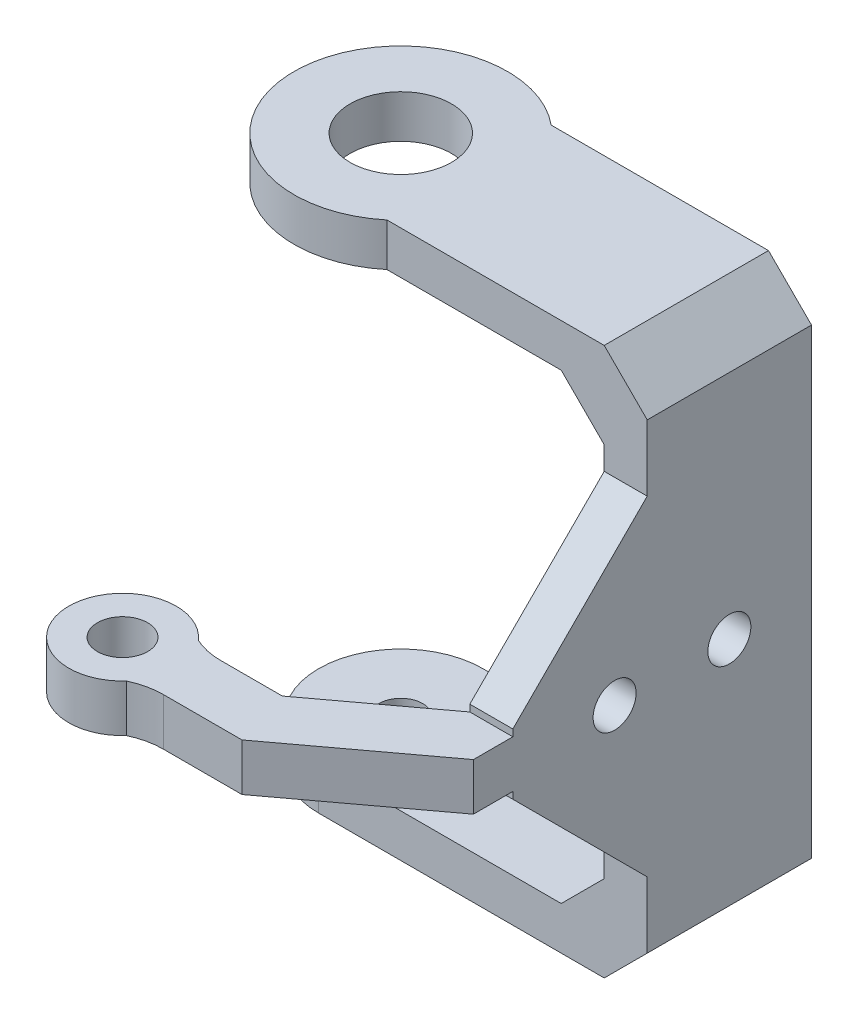
SolidWorks part; units mm, degrees
ref_plane "Front Plane" through (0, 0, 0) normal (0, 0, 1) x (1, 0, 0)
ref_plane "Top Plane" through (0, 0, 0) normal (0, 1, 0) x (1, 0, 0)
ref_plane "Right Plane" through (0, 0, 0) normal (1, 0, 0) x (0, 0, -1)
sketch "Sketch1" plane through (0, 0, 0) normal (0, 0, 1) x (1, 0, 0)
  line L0 (32.1661, 36.798) -> (35.1661, 39.798)
  line L1 (35.1661, 39.798) -> (38.1661, 36.798)
  line L2 (38.1661, 36.798) -> (38.1661, 4.578)
  line L3 (38.1661, 4.578) -> (35.1661, 1.578)
  line L4 (35.1661, 1.578) -> (32.1661, 4.578)
  line L5 (32.1661, 4.578) -> (35.1661, 7.578)
  line L6 (35.1661, 7.578) -> (35.1661, 33.798)
  line L7 (35.1661, 33.798) -> (32.1661, 36.798)
extrude "Boss-Extrude1" add sketch "Sketch1" along normal blind 5.73 and the other way blind 5.73
sketch "Sketch2" plane through (0, 0, 5.73) normal (0, 0, 1) x (1, 0, 0)
  line L0 (32.1661, 36.798) -> (20.0061, 36.798)
  line L2 (32.1661, 39.7973) -> (35.1655, 39.7973)
  line L3 (35.1661, 39.798) -> (32.1661, 36.798) construction
  line L4 (32.1661, 39.7973) -> (20.0061, 39.7973)
  line L5 (20.0061, 39.7973) -> (20.0061, 36.798)
  line L6 (35.1655, 39.7973) -> (32.1661, 36.798)
extrude "Boss-Extrude2" add sketch "Sketch2" against normal up to vertex (11.46 mm away) up to point (32.1661, 36.798, -5.73)
sketch "Sketch3" plane through (0, 0, 5.73) normal (0, 0, 1) x (1, 0, 0)
  line L0 (32.1661, 4.578) -> (35.1661, 1.578)
  line L1 (35.1661, 1.578) -> (32.1661, 1.578)
  line L3 (32.1661, 4.578) -> (20.0061, 4.578)
  line L4 (20.0061, 4.578) -> (20.0061, 1.578)
  line L5 (20.0061, 1.578) -> (32.1661, 1.578)
extrude "Boss-Extrude3" add sketch "Sketch3" against normal up to vertex (11.46 mm away) up to point (32.1661, 4.578, -5.73)
sketch "Sketch4" plane through (0, 39.7973, 0) normal (0, 1, 0) x (1, 0, 0)
  line L0 (20.0061, 5.73) -> (20.0061, -5.73)
  arc A0 (20.0061, 5.73) -> (20.0061, -5.73) centre (15.2449, 0) ccw
extrude "Boss-Extrude4" add sketch "Sketch4" against normal up to vertex (2.9993 mm away) up to point (20.0061, 36.798, 5.73)
sketch "Sketch7" plane through (0, 39.7973, 0) normal (0, 1, 0) x (1, 0, 0)
  circle A1 centre (15.2449, 0) radius 3.54
extrude "Cut-Extrude2" cut sketch "Sketch7" against normal up to vertex (2.9993 mm away) up to point (20.0061, 36.798, -5.73)
sketch "Sketch9" plane through (0, 1.578, 0) normal (0, -1, 0) x (-1, 0, 0)
  line L0 (-20.0061, -5.73) -> (-15.2449, -5.73)
  line L2 (-15.2449, 5.73) -> (-20.0061, 5.73)
  line L3 (-20.0061, 5.73) -> (-20.0061, -5.73)
  arc A0 (-15.2449, -5.73) -> (-15.2449, 5.73) centre (-15.2449, 0) ccw
extrude "Boss-Extrude5" add sketch "Sketch9" against normal blind 3 contours L0 A0 L2 L3
sketch "Sketch11" plane through (0, 1.578, 0) normal (0, -1, 0) x (-1, 0, 0)
  circle A1 centre (-15.2449, 0) radius 1.52
extrude "Cut-Extrude3" cut sketch "Sketch11" against normal blind 3
sketch "Sketch12" plane through (38.1661, 0, 0) normal (1, 0, 0) x (0, 0, -1)
  line L0 (-5.73, 32.188) -> (-5.73, 9.188)
  line L1 (-5.73, 4.578) -> (-5.73, 36.798) construction
  line L2 (-15.1062, 22.8118) -> (-15.1062, 18.5642)
  line L3 (-5.73, 32.188) -> (-15.1062, 22.8118)
  line L4 (-5.73, 9.188) -> (-15.1062, 18.5642)
extrude "Boss-Extrude6" add sketch "Sketch12" against normal up to vertex (3 mm away) up to point (35.1661, 33.798, 5.73)
ref_plane "Plane1" through (0, 20.688, 0) normal (0, -1, 0) x (-1, 0, 0)
sketch "Sketch15" plane through (0, 20.688, 0) normal (0, -1, 0) x (-1, 0, 0)
  line L0 (-35.1661, -15.1062) -> (-38.1661, -15.1062)
  line L1 (-38.1661, -15.1062) -> (-38.1661, -17.8562)
  line L2 (-38.1661, -17.8562) -> (-28.9052, -24.7415)
  line L3 (-35.1661, -15.1062) -> (-27.6617, -20.6836)
  line L4 (-28.9052, -24.7415) -> (-23.4252, -24.7415)
  line L5 (-27.6617, -20.6836) -> (-23.3433, -20.6836)
  arc A0 (-23.3433, -20.6836) -> (-21.3674, -20.2473) centre (-23.3433, -15.9908) ccw
  arc A1 (-23.4252, -24.7415) -> (-21.3186, -25.207) centre (-23.4252, -29.7415) cw
  arc A2 (-21.3186, -25.207) -> (-21.3674, -20.2473) centre (-18.5303, -22.6995) ccw
extrude "Boss-Extrude7" add sketch "Sketch15" along normal blind 1.65 and the other way blind 1.65 contours A2 A0 L5 L3 L0 L1 L2 L4 A1
sketch "Sketch16" plane through (0, 19.038, 0) normal (0, -1, 0) x (-1, 0, 0)
  circle A0 centre (-18.5303, -22.6995) radius 1.75
extrude "Cut-Extrude4" cut sketch "Sketch16" against normal up to vertex (3.3 mm away) up to point (21.3186, 22.338, 25.207)
sketch "Sketch17" plane through (38.1661, 0, 0) normal (1, 0, 0) x (0, 0, -1)
  circle A0 centre (-8.0062, 20.688) radius 1.5
  circle A1 centre (0, 20.688) radius 1.5
extrude "Cut-Extrude5" cut sketch "Sketch17" against normal up to vertex (3 mm away) up to point (35.1661, 33.798, -5.73)
